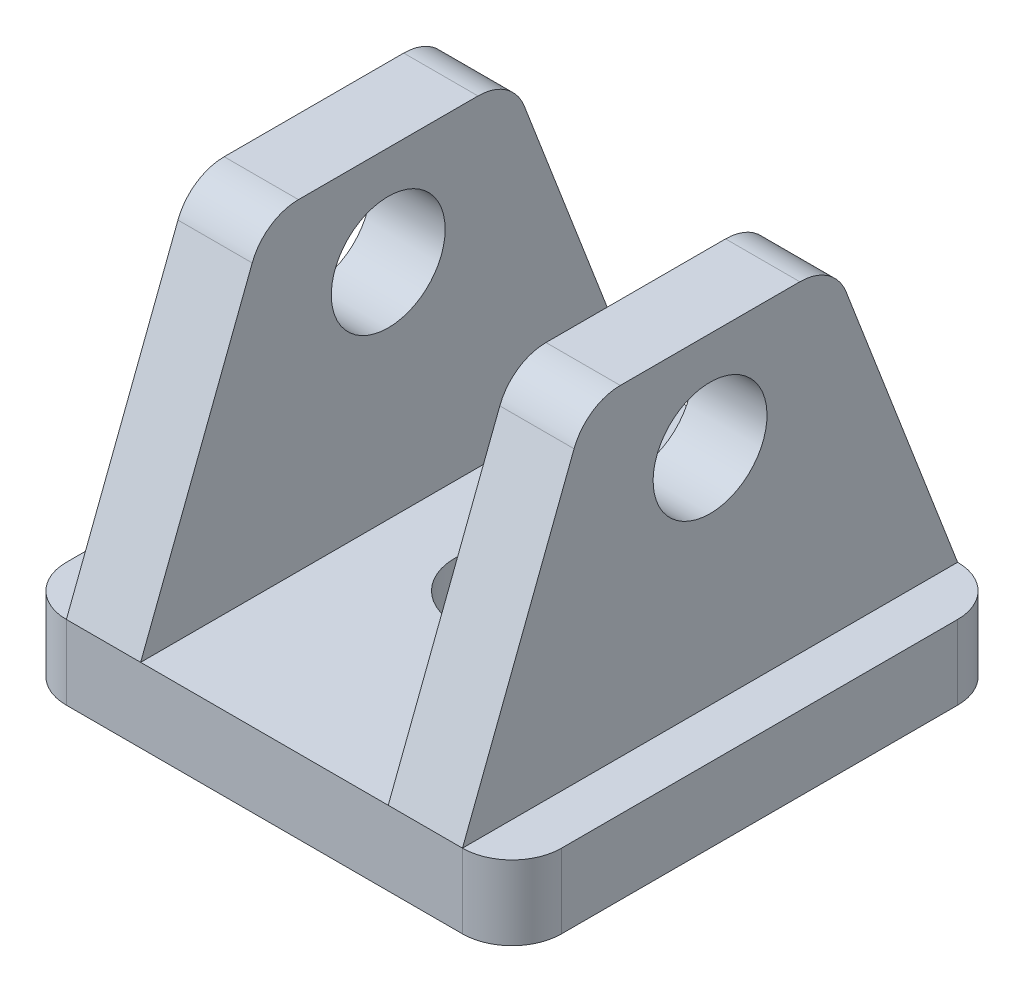
SolidWorks part; units mm, degrees
ref_plane "Front Plane" through (0, 0, 0) normal (0, 0, 1) x (1, 0, 0)
ref_plane "Top Plane" through (0, 0, 0) normal (0, 1, 0) x (1, 0, 0)
ref_plane "Right Plane" through (0, 0, 0) normal (1, 0, 0) x (0, 0, -1)
sketch "Sketch1" plane through (0, 0, 0) normal (0, 1, 0) x (1, 0, 0)
  line L0 (12.7, 0) -> (12.7, 12.7) construction
  line L1 (0, 0) -> (25.4, 0)
  line L2 (0, 0) -> (0, 25.4)
  line L3 (0, 25.4) -> (25.4, 25.4)
  line L4 (25.4, 0) -> (25.4, 25.4)
  circle A0 centre (12.7, 12.7) radius 2.921
  dimension "D3" = 5.842
  dimension "D1" = 25.4
  dimension "D2" = 25.4
  dimension "D4" = 12.7
extrude "Boss-Extrude1" add sketch "Sketch1" along normal blind 3.81
fillet "Fillet1" radius 2.54 4 edges at (0, 1.905, -25.4) (25.4, 1.905, -25.4) (25.4, 1.905, 0) (0, 1.905, 0)
sketch "Sketch2" plane through (0, 3.81, 0) normal (0, 1, 0) x (1, 0, 0)
  line L0 (2.54, 0) -> (22.86, 0) construction
  line L1 (2.54, 25.4) -> (6.35, 25.4)
  line L2 (2.54, 25.4) -> (2.54, 0)
  line L3 (2.54, 0) -> (6.35, 0)
  line L4 (6.35, 25.4) -> (6.35, 0)
  line L6 (22.86, 25.4) -> (19.05, 25.4)
  line L7 (22.86, 25.4) -> (22.86, 0)
  line L8 (22.86, 0) -> (19.05, 0)
  line L9 (19.05, 25.4) -> (19.05, 0)
  dimension "D1" = 3.81
ref_plane "Plane1" through (0, 20.32, 0) normal (0, 1, 0) x (1, 0, 0)
sketch "Sketch3" plane through (0, 20.32, 0) normal (0, 1, 0) x (1, 0, 0)
  line L0 (2.54, 25.4) -> (2.54, 0) construction
  line L1 (2.54, 19.05) -> (6.35, 19.05)
  line L2 (2.54, 19.05) -> (2.54, 6.35)
  line L3 (2.54, 6.35) -> (6.35, 6.35)
  line L4 (6.35, 19.05) -> (6.35, 6.35)
  line L5 (6.35, 25.4) -> (6.35, 0) construction
  line L6 (2.54, 0) -> (6.35, 0) construction
  line L7 (2.54, 25.4) -> (6.35, 25.4) construction
  line L8 (19.05, 25.4) -> (19.05, 0) construction
  line L9 (19.05, 19.05) -> (22.86, 19.05)
  line L10 (19.05, 19.05) -> (19.05, 6.35)
  line L11 (19.05, 6.35) -> (22.86, 6.35)
  line L12 (22.86, 19.05) -> (22.86, 6.35)
  line L13 (22.86, 25.4) -> (22.86, 0) construction
  line L14 (22.86, 25.4) -> (19.05, 25.4) construction
  line L15 (22.86, 0) -> (19.05, 0) construction
  dimension "D1" = 6.35
  dimension "D2" = 6.35
  dimension "D3" = 6.35
  dimension "D4" = 6.35
loft "Loft2" add section "Sketch2" section "Sketch3" connector at (6.35, 3.81, 0) connector at (6.35, 20.32, -6.35)
loft "Loft3" add section "Sketch2<3>" section "Sketch3<3>" connector at (22.86, 3.81, -25.4) connector at (22.86, 20.32, -19.05)
sketch "Sketch2<3>" plane through (0, 3.81, 0) normal (0, 1, 0) x (1, 0, 0) same geometry as "Sketch2"
sketch "Sketch3<3>" plane through (0, 20.32, 0) normal (0, 1, 0) x (1, 0, 0) same geometry as "Sketch3"
sketch "Sketch4" plane through (2.54, 0, 0) normal (-1, 0, 0) x (0, 0, 1)
  line L0 (-12.7, 20.32) -> (-12.7, 15.24) construction
  line L1 (-19.05, 20.32) -> (-6.35, 20.32) construction
  circle A0 centre (-12.7, 15.24) radius 2.921
  dimension "D1" = 5.842
  dimension "D2" = 5.08
extrude "Cut-Extrude1" cut sketch "Sketch4" against normal through all
fillet "Fillet2" radius 2.54 4 edges
